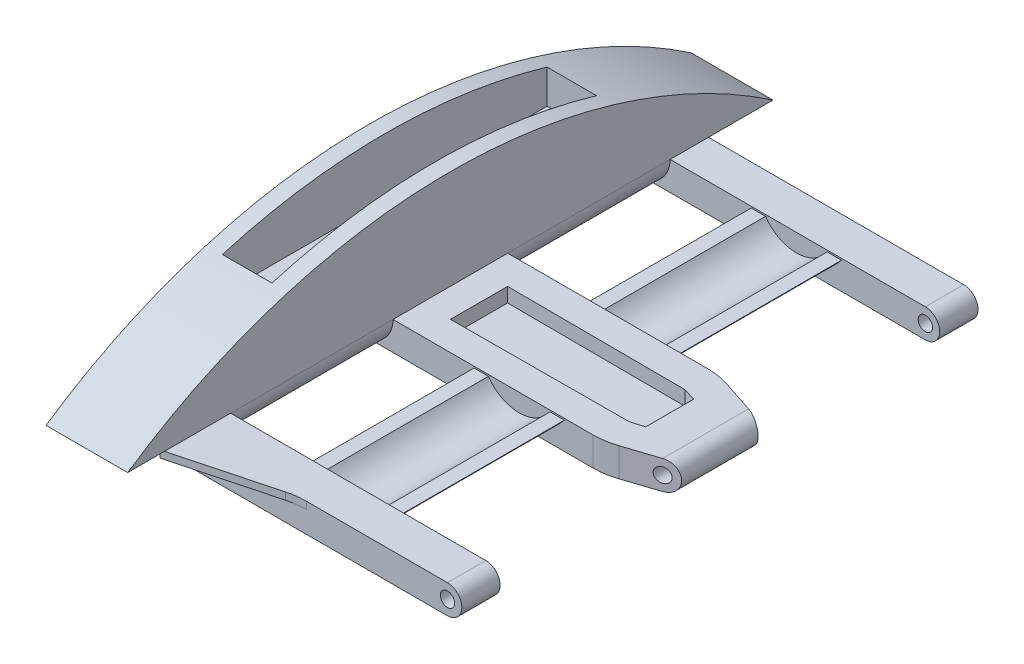
SolidWorks part; units mm, degrees
ref_plane "Front Plane" through (0, 0, 0) normal (0, 0, 1) x (1, 0, 0)
ref_plane "Top Plane" through (0, 0, 0) normal (0, 1, 0) x (1, 0, 0)
ref_plane "Right Plane" through (0, 0, 0) normal (1, 0, 0) x (0, 0, -1)
sketch "Sketch2" plane through (0, 0, 0) normal (0, 1, 0) x (1, 0, 0)
  line L4 (0, 45) -> (0, 0)
  line L5 (0, 0) -> (10, 0)
  line L6 (10, 0) -> (10, 45)
  line L7 (10, 45) -> (0, 45)
  line L8 (0, 40.5) -> (10, 40.5) construction
  line L9 (0, 4.5) -> (10, 4.5) construction
  dimension "D1" = 45
  dimension "D2" = 4.5
  dimension "D3" = 4.5
  dimension "D4" = 10
sketch "Sketch3" plane through (0, 0, 0) normal (1, 0, 0) x (0, 0, -1)
  line L0 (0, 0) -> (45, 0)
  arc A0 (0, 0) -> (45, 0) centre (22.5, -33.0719) cw
  dimension "D1" = 40
extrude "Boss-Extrude1" add sketch "Sketch3" along normal blind 2.7
sketch "Sketch4" plane through (0, 0, 0) normal (0, -1, 0) x (1, 0, 0)
  line L0 (0, -45) -> (0, 0) construction
  line L1 (2.7, 0) -> (2.7, -45) construction
  line L2 (2.7, -22.5) -> (30.4189, -22.5) construction
  line L3 (2.7, -44.1622) -> (2.7, -45)
  line L4 (2.7, -45) -> (0, -45)
  line L5 (0, -45) -> (0, -44.1622)
  line L6 (2.7, 0) -> (0, 0)
  line L7 (2.7, -0.8378) -> (2.7, 0)
  line L8 (0, 0) -> (0, -0.8378)
  arc A0 (0, -44.1622) -> (2.7, -44.1622) centre (1.35, -43.4934) ccw
  arc A1 (0, -0.8378) -> (2.7, -0.8378) centre (1.35, -1.5066) cw
  point P3 (1.35, -45)
  dimension "D1" = 1.5066
sketch "Sketch6" plane through (0, 0, 0) normal (0, -1, 0) x (1, 0, 0)
  line L1 (0, -4.5) -> (21.5, -4.5)
  line L2 (0, -4.5) -> (0, -40.5)
  line L3 (0, -40.5) -> (21.5, -40.5)
  line L4 (21.5, -4.5) -> (21.5, -40.5)
  line L6 (0, -4.5) -> (10, -4.5) construction
  line L7 (0, -40.5) -> (10, -40.5) construction
  line L8 (0, -45) -> (0, 0) construction
  dimension "D1" = 21.5
extrude "Boss-Extrude2" add sketch "Sketch6" along normal blind 2
sketch "Sketch7" plane through (0, 0, 0) normal (0, 1, 0) x (1, 0, 0)
  line L0 (21.5, 22.5) -> (-9.3767, 22.5) construction
  line L1 (21.5, 40.5) -> (21.5, 4.5) construction
  line L2 (2.7, 0) -> (2.7, 45) construction
  line L3 (2.7, 26.5) -> (21.5, 26.5)
  line L4 (2.7, 26.5) -> (2.7, 37.827)
  line L5 (2.7, 37.827) -> (21.5, 37.827)
  line L6 (21.5, 26.5) -> (21.5, 37.827)
  line L7 (2.7, 32.1635) -> (21.5, 32.1635) construction
  line L9 (2.7, 7.173) -> (21.5, 7.173)
  line L10 (21.5, 18.5) -> (21.5, 7.173)
  line L11 (2.7, 18.5) -> (21.5, 18.5)
  line L12 (2.7, 18.5) -> (2.7, 7.173)
  line L13 (2.7, 40.5) -> (21.5, 40.5) construction
  dimension "D1" = 2.673
  dimension "D2" = 8
extrude "Cut-Extrude3" cut sketch "Sketch7" against normal blind 2 contours L11 L9 | L5 L9 L3 L11 | L9 L10 L11 L12 region at (12.1, 0, -32.1635) region at (12.1, 0, -12.8365)
sketch "Sketch8" plane through (0, 0, -40.5) normal (0, 0, -1) x (-1, 0, 0)
  line L0 (-21.5, -2) -> (-21.5, 0) construction
  line L1 (-2.7, 0) -> (-21.5, 0) construction
  line L2 (0, -2) -> (-21.5, -2) construction
  line L3 (-20.5, 0) -> (-21.5, 0)
  line L4 (-21.5, 0) -> (-21.5, -2)
  line L5 (-21.5, -2) -> (-20.5, -2)
  circle A0 centre (-20.5, -1) radius 1
  line M3 (-2.7, 0) -> (-21.5, 0)
  line M4 (-21.5, 0) -> (-21.5, -2)
  line M5 (-21.5, -2) -> (0, -2)
extrude "Cut-Extrude4" cut sketch "Sketch8" against normal through all contours A0 M3 M4 | A0 L4 M5 region at (21.2766, -0.2234, -40.5) region at (21.2766, -1.7766, -40.5)
sketch "Sketch10" plane through (0, 0, -40.5) normal (0, 0, -1) x (-1, 0, 0)
  circle A0 centre (-20.5, -1) radius 0.5
  dimension "D1" = 1
extrude "Cut-Extrude5" cut sketch "Sketch10" against normal through all
sketch "Sketch11" plane through (0, 0, -40.5) normal (0, 0, -1) x (-1, 0, 0)
  line L0 (0, 0) -> (-10, 0) construction
  line L1 (-11.3244, 0) -> (-8.2339, 0)
  line L2 (-11.3244, 0) -> (-11.3244, -2)
  line L3 (-11.3244, -2) -> (-8.2339, -2)
  line L4 (-8.2339, 0) -> (-8.2339, -2)
  line L5 (0, -2) -> (-20.5, -2) construction
sketch "Sketch22" plane through (0, -2, 0) normal (0, -1, 0) x (1, 0, 0)
  line L0 (0, -45) -> (0, 0) construction
  line L1 (0, -26.5) -> (2.3, -26.5)
  line L2 (0, -26.5) -> (0, -18.5)
  line L3 (0, -18.5) -> (2.3, -18.5)
  line L4 (2.3, -26.5) -> (2.3, -18.5)
  line L6 (2.7, -26.5) -> (20.5, -26.5) construction
  line L7 (2.7, -18.5) -> (20.5, -18.5) construction
  line L13 (0, -40.5) -> (10, -40.5) construction
  line L14 (0, -4.5) -> (2.3, -4.5)
  line L15 (0, -4.5) -> (0, -7.173)
  line L16 (0, -7.173) -> (2.3, -7.173)
  line L17 (2.3, -4.5) -> (2.3, -7.173)
  line L18 (0, -37.827) -> (2.3, -37.827)
  line L19 (0, -37.827) -> (0, -40.5)
  line L20 (0, -40.5) -> (2.3, -40.5)
  line L21 (2.3, -37.827) -> (2.3, -40.5)
  line L22 (2.7, -37.827) -> (20.5, -37.827) construction
  line L23 (2.7, -7.173) -> (20.5, -7.173) construction
  dimension "D1" = 2.3
  dimension "D2" = 2.3
  dimension "D3" = 2.3
sketch "Sketch23" plane through (0, 0, 0) normal (0, 1, 0) x (1, 0, 0)
  line L0 (11.878, 16.6727) -> (21.5, 19.833)
  line L1 (21.5, 18.5) -> (21.5, 26.5) construction
  line L2 (21.5, 19.833) -> (21.5, 13.5123)
  line L3 (21.5, 13.5123) -> (11.878, 16.6727)
  line L4 (21.5, 22.5) -> (-3.6609, 22.5) construction
  line L5 (21.5, 25.167) -> (21.5, 31.4877)
  line L6 (11.878, 28.3273) -> (21.5, 25.167)
  line L7 (21.5, 31.4877) -> (11.878, 28.3273)
  point P7 (21.5, 16.6727)
extrude "Cut-Extrude15" cut sketch "Sketch23" against normal blind 16 contours L5 L7 L6 | L3 L0 L2
fillet "Fillet6" radius 5 2 edges at (17.4416, -1, -26.5) (17.4416, -1, -18.5)
sketch "Sketch31" plane through (0, 0, -40.5) normal (0, 0, -1) x (-1, 0, 0)
  line L3 (-14.6564, -0.1066) -> (-8.3564, -0.1066)
  arc A2 (-14.6564, -0.1066) -> (-8.3564, -0.1066) centre (-11.5064, 2.3586) ccw
  dimension "D2" = 4
  dimension "D1" = 6.3
extrude "Boss-Extrude6" add sketch "Sketch31" against normal up to surface (36 mm away) up to face at (20, -1, -4.5)
sketch "Sketch30" plane through (0, 0, 0) normal (0, 1, 0) x (1, 0, 0)
  line L0 (2.7, 26.5) -> (2.7, 18.5)
  line L1 (2.7, 18.5) -> (17.4315, 18.5628)
  line L2 (17.4315, 18.5628) -> (20, 19.3403)
  line L3 (20, 19.3403) -> (20, 25.6597)
  line L4 (20, 25.6597) -> (17.4315, 26.4372)
  line L5 (17.4315, 26.4372) -> (2.7, 26.5)
  line L6 (17.1313, 24.4385) -> (4.7, 24.4915)
  line L7 (4.7, 24.4915) -> (4.7, 20.5085)
  line L8 (4.7, 20.5085) -> (17.1313, 20.5615)
  line L9 (17.1313, 20.5615) -> (18, 20.8245)
  line L10 (18, 20.8245) -> (18, 24.1755)
  line L11 (18, 24.1755) -> (17.1313, 24.4385)
  arc A0 (16.6415, 18.5) -> (18.2017, 18.7497) centre (16.6415, 23.5) ccw construction
  arc A1 (18.2017, 26.2503) -> (16.6415, 26.5) centre (16.6415, 21.5) ccw construction
  dimension "D1" = 2
extrude "Cut-Extrude18" cut sketch "Sketch30" against normal blind 1 contours L6 L7 L8 L9 L10 L11
ref_plane "Plane1" through (0, 6.9281, 0) normal (0, 1, 0) x (1, 0, 0)
sketch "Sketch33" plane through (0, 0, -40.5) normal (0, 0, -1) x (-1, 0, 0)
  line L1 (-13.6564, -0.1066) -> (-9.3564, -0.1066)
  line L2 (-14.6564, -0.1066) -> (-8.3564, -0.1066) construction
  arc A1 (-13.6564, -0.1066) -> (-9.3564, -0.1066) centre (-11.5064, 1.3586) ccw
  arc A3 (-14.6564, -0.1066) -> (-8.3564, -0.1066) centre (-11.5064, 2.3586) ccw construction
  dimension "D1" = 1
  dimension "D2" = 1
  dimension "D3" = 1
sketch "Sketch36" plane through (0, 0, -37.827) normal (0, 0, 1) x (1, 0, 0)
  line L0 (9.3564, -0.1066) -> (13.6564, -0.1066)
  arc A0 (9.3564, -0.1066) -> (13.6564, -0.1066) centre (11.5064, 1.3586) ccw construction
  arc A1 (9.3564, -0.1066) -> (13.6564, -0.1066) centre (11.5064, 1.3586) ccw
extrude "Cut-Extrude22" cut sketch "Sketch36" along normal up to surface (11.327 mm away) up to face at (11.5064, -0.874, -26.5)
sketch "Sketch37" plane through (0, 0, -7.173) normal (0, 0, -1) x (-1, 0, 0)
  line L0 (-13.6564, -0.1066) -> (-9.3564, -0.1066)
  arc A0 (-13.6564, -0.1066) -> (-9.3564, -0.1066) centre (-11.5064, 1.3586) ccw construction
  arc A1 (-13.6564, -0.1066) -> (-9.3564, -0.1066) centre (-11.5064, 1.3586) ccw
extrude "Cut-Extrude23" cut sketch "Sketch37" along normal up to surface (11.327 mm away) up to face at (11.5064, -0.874, -18.5)
sketch "Sketch42" plane through (0, 0, 0) normal (-1, 0, 0) x (0, 0, 1)
  line L0 (-45, 0) -> (-40.5, 0)
  line L1 (-40.5, 0) -> (-40.5, -2)
  line L2 (-40.5, -2) -> (-4.5, -2)
  line L3 (-4.5, -2) -> (-4.5, 0)
  line L4 (-4.5, 0) -> (0, 0)
  arc A3 (0, 0) -> (-45, 0) centre (-22.5, -33.0719) ccw construction
  arc A4 (0, 0) -> (-45, 0) centre (-22.5, -33.0719) ccw
extrude "Boss-Extrude10" add sketch "Sketch42" along normal blind 3
sketch "Sketch43" plane through (0, -2, 0) normal (0, -1, 0) x (1, 0, 0)
  line L0 (-3, -40.5) -> (-3, -4.5) construction
  line L1 (-3, -4.5) -> (-0.7, -4.5)
  line L2 (-3, -4.5) -> (-3, -7.173)
  line L3 (-3, -7.173) -> (-0.7, -7.173)
  line L4 (-0.7, -4.5) -> (-0.7, -7.173)
  line L5 (-3, -18.5) -> (-0.7, -18.5)
  line L6 (-3, -18.5) -> (-3, -26.5)
  line L7 (-3, -26.5) -> (-0.7, -26.5)
  line L8 (-0.7, -18.5) -> (-0.7, -26.5)
  line L9 (-3, -40.5) -> (20.5, -40.5) construction
  line L10 (-3, -37.827) -> (-0.7, -37.827)
  line L11 (-3, -37.827) -> (-3, -40.5)
  line L12 (-3, -40.5) -> (-0.7, -40.5)
  line L13 (-0.7, -37.827) -> (-0.7, -40.5)
  line L14 (2.7, -37.827) -> (20.5, -37.827) construction
  line L15 (2.7, -18.5) -> (16.6415, -18.5) construction
  line L16 (2.7, -26.5) -> (16.6415, -26.5) construction
  line L17 (2.7, -7.173) -> (20.5, -7.173) construction
  dimension "D1" = 2.3
  dimension "D2" = 2.3
  dimension "D3" = 2.3
revolve "Cut-Revolve7" cut sketch "Sketch43" angle 360 about L2
sketch "Sketch45" plane through (0, 0, -7.173) normal (0, 0, 1) x (1, 0, 0)
  line L0 (-3, -2) -> (-3, 0.3) construction
  line L2 (-0.7, -2) -> (-3, -2) construction
  circle A0 centre (-2, -1) radius 0.5
  dimension "D1" = 1
  dimension "D2" = 1
  dimension "D3" = 1
extrude "Cut-Extrude26" cut sketch "Sketch45" against normal through all
ref_plane "Plane3" through (0, 6.9281, 0) normal (0, 1, 0) x (1, 0, 0)
sketch "Sketch47" plane through (0, 6.9281, 0) normal (0, 1, 0) x (1, 0, 0)
  line L0 (2.7, 0) -> (2.7, 45) construction
  line L1 (-1.877, 33.8191) -> (1.577, 33.8191)
  line L2 (-1.877, 33.8191) -> (-1.877, 11.1809)
  line L3 (-1.877, 11.1809) -> (1.577, 11.1809)
  line L4 (1.577, 33.8191) -> (1.577, 11.1809)
  line L5 (2.7, 45) -> (-3, 45) construction
  point P6 (2.7, 22.5)
  point P7 (1.577, 22.5)
  point P8 (-0.15, 45)
  point P11 (-0.15, 33.8191)
  dimension "D1" = 1.123
extrude "Cut-Extrude27" cut sketch "Sketch47" against normal blind 4
fillet "Fillet13" radius 2 2 edges at (2.7, -2, -12.8365) (2.7, -2, -32.1635)
fillet "Fillet15" radius 1 2 edges at (-3, -2, -32.1635) (-3, -2, -12.8365)
ref_plane "Plane4" through (0, 0, -22.5) normal (0, 0, 1) x (1, 0, 0)
sketch "Sketch27" plane through (0, 0, 0) normal (0, -1, 0) x (1, 0, 0)
  line L1 (2.45, -4.5) -> (10, -4.5)
  line L2 (10, -4.5) -> (2.45, -2.5)
  line L3 (2.45, -2.5) -> (2.45, -4.5)
  line L4 (2.7, 0) -> (2.7, -4.5) construction
  dimension "D1" = 0.25
  dimension "D2" = 2
extrude "Boss-Extrude5" add sketch "Sketch27" along normal blind 0.5
fillet "Fillet7" radius 5 1 edges at (10, -0.25, -4.5)
